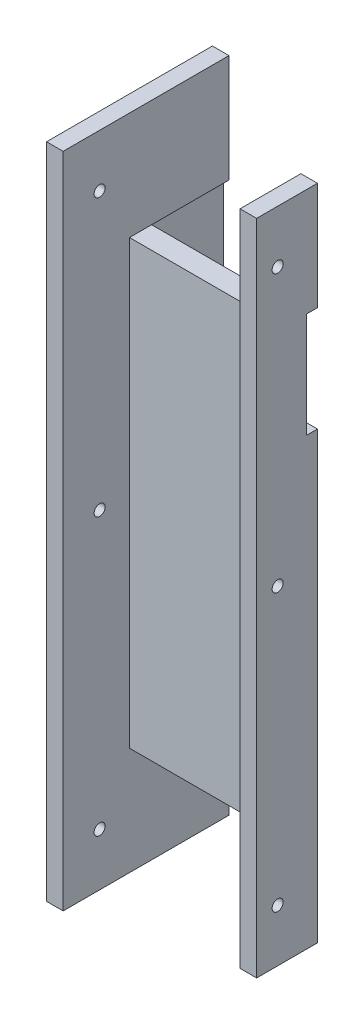
SolidWorks part; units mm, degrees
ref_plane "前视基准面" through (0, 0, 0) normal (0, 0, 1) x (1, 0, 0)
ref_plane "上视基准面" through (0, 0, 0) normal (0, 1, 0) x (1, 0, 0)
ref_plane "右视基准面" through (0, 0, 0) normal (1, 0, 0) x (0, 0, -1)
other "Configuration Table"
sketch "草图1" plane through (0, 0, 0) normal (1, 0, 0) x (0, 0, -1)
  line L0 (0, 31.9197) -> (0, -34.0629) construction
  line L1 (-4, -29.75) -> (1.5, -29.75)
  line L2 (-4, -29.75) -> (-4, 29.75)
  line L3 (-4, 29.75) -> (1.5, 29.75)
  line L4 (1.5, -29.75) -> (1.5, 29.75)
  line L5 (-4, -29.75) -> (1.5, 29.75) construction
  line L6 (-4, 29.75) -> (1.5, -29.75) construction
  line L7 (18.5819, 0) -> (-18.5363, 0) construction
  point P0 (-1.25, 0)
  dimension "D1" = 59.5
  dimension "D2" = 5.5
  dimension "D3" = 1.25
extrude "凸台-拉伸1" add sketch "草图1" along normal blind 1.5
sketch "草图2" plane through (0, 0, 0) normal (-1, 0, 0) x (0, 0, 1)
  line L2 (-1.5, -20) -> (1.5, -20)
  line L3 (-1.5, -20) -> (-1.5, 20)
  line L4 (-1.5, 20) -> (1.5, 20)
  line L5 (1.5, -20) -> (1.5, 20)
  line L6 (-1.5, -20) -> (1.5, 20) construction
  line L7 (-1.5, 20) -> (1.5, -20) construction
  point P1 (0, 0)
  dimension "D1" = 40
extrude "凸台-拉伸2" add sketch "草图2" along normal blind 12.5
sketch "草图3" plane through (-12.5, 0, 0) normal (-1, 0, 0) x (0, 0, 1)
  line L1 (-7.5, -29.75) -> (7.5, -29.75)
  line L2 (-7.5, -29.75) -> (-7.5, 29.75)
  line L3 (-7.5, 29.75) -> (7.5, 29.75)
  line L4 (7.5, -29.75) -> (7.5, 29.75)
  line L5 (-7.5, -29.75) -> (7.5, 29.75) construction
  line L6 (-7.5, 29.75) -> (7.5, -29.75) construction
  point P0 (0, 0)
  dimension "D1" = 15
  dimension "D2" = 59.5
extrude "凸台-拉伸3" add sketch "草图3" along normal blind 1.5
sketch "草图4" plane through (0, 0, -1.5) normal (0, 0, -1) x (-1, 0, 0)
  line L0 (-1.5, -29.75) -> (-1.5, 29.75) construction
  line L1 (12.5, 20) -> (-1.5, 20)
  line L2 (12.5, 20) -> (12.5, 10.5)
  line L3 (12.5, 10.5) -> (-1.5, 10.5)
  line L4 (-1.5, 20) -> (-1.5, 10.5)
  dimension "D1" = 9.5
extrude "切除-拉伸1" cut sketch "草图4" against normal blind 1
sketch "草图5" plane through (-12.5, 0, 0) normal (1, 0, 0) x (0, 0, -1)
  line L0 (7.5, 29.75) -> (7.5, -29.75) construction
  line L1 (0.5, 10.5) -> (7.5, 10.5)
  line L2 (0.5, 10.5) -> (0.5, 20)
  line L3 (0.5, 20) -> (7.5, 20)
  line L4 (7.5, 10.5) -> (7.5, 20)
  line L5 (-1.5, 20) -> (0.5, 20) construction
extrude "切除-拉伸2" cut sketch "草图5" against normal blind 0.5
sketch "草图6" plane through (-12.5, 0, 0) normal (1, 0, 0) x (0, 0, -1)
  line L0 (7.5, -29.75) -> (-7.5, -29.75) construction
  line L1 (-7.5, -29.75) -> (-7.5, 29.75) construction
  line L2 (7.5, 10.5) -> (7.5, -29.75) construction
  line L3 (-4.2, -25) -> (-4.2, 0) construction
  line L4 (3.8, -16.5) -> (3.8, 7.5) construction
  circle A0 centre (-4.2, -25) radius 0.5
  circle A1 centre (3.8, -16.5) radius 0.5
  circle A2 centre (-4.2, 0) radius 0.5
  circle A3 centre (-4.2, 25) radius 0.5
  circle A4 centre (3.8, 7.5) radius 0.5
  dimension "D1" = 1
  dimension "D2" = 4.75
  dimension "D3" = 3.3
  dimension "D4" = 13.25
  dimension "D5" = 3.7
  dimension "D7" = 25
  dimension "D9" = 24
  dimension "D6" = 3
  dimension "D8" = 2
extrude "切除-拉伸3" cut sketch "草图6" against normal blind 2.2
sketch "草图7" plane through (1.5, 0, 0) normal (1, 0, 0) x (0, 0, -1)
  line L0 (-2.1, 33.1033) -> (-2.1, -35.3509) construction
  line L3 (-4, -29.75) -> (1.5, -29.75) construction
  line L4 (-2.1, -25) -> (-2.1, 0) construction
  line L5 (1.5, -29.75) -> (1.5, 10.5) construction
  circle A0 centre (-2.1, -25) radius 0.5
  circle A1 centre (-2.1, 0) radius 0.5
  circle A2 centre (-2.1, 25) radius 0.5
  dimension "D1" = 1
  dimension "D2" = 4.75
  dimension "D4" = 25
  dimension "D5" = 3.6
  dimension "D3" = 3
extrude "切除-拉伸4" cut sketch "草图7" against normal blind 4
